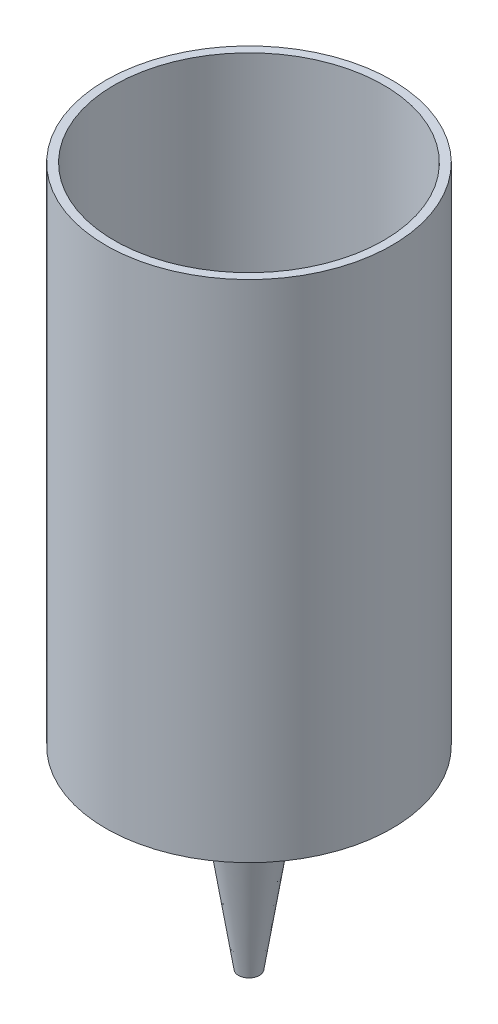
SolidWorks part; units mm, degrees
ref_plane "Front Plane" through (0, 0, 0) normal (0, 0, 1) x (1, 0, 0)
ref_plane "Top Plane" through (0, 0, 0) normal (0, 1, 0) x (1, 0, 0)
ref_plane "Right Plane" through (0, 0, 0) normal (1, 0, 0) x (0, 0, -1)
sketch "Sketch1" plane through (0, 0, 0) normal (0, 0, 1) x (1, 0, 0)
  line L4 (-21.59, 105.41) -> (0, 105.41)
  line L5 (0, 105.41) -> (0, 0)
  line L6 (-21.59, 105.41) -> (-21.59, 29.21)
  line L7 (-21.59, 29.21) -> (-5.5174, 25.4)
  line L8 (-5.5174, 25.4) -> (-1.5875, 0)
  line L9 (-1.5875, 0) -> (0, 0)
  dimension "D1" = 21.59
  dimension "D2" = 76.2
  dimension "D3" = 25.4
  dimension "D4" = 1.5875
  dimension "D5" = 3.81
revolve "Revolve1" add sketch "Sketch1" angle 360 about L5 region at (-10.2556, 63.5257, 0)
shell "Shell1" thickness 1.27 removed face at (-21.59, 105.41, 0)
sketch "Sketch3" plane through (0, 0, 0) normal (0, -1, 0) x (1, 0, 0)
  circle A0 centre (0, 0) radius 1.0795
  circle A1 centre (0, 0) radius 1.5875 construction
  dimension "D1" = 0.508
extrude "Cut-Extrude1" cut sketch "Sketch3" against normal through all and the other way through all
sketch "Sketch4" plane through (0, 105.41, 0) normal (0, 1, 0) x (1, 0, 0)
  point P0 (0, 0)
